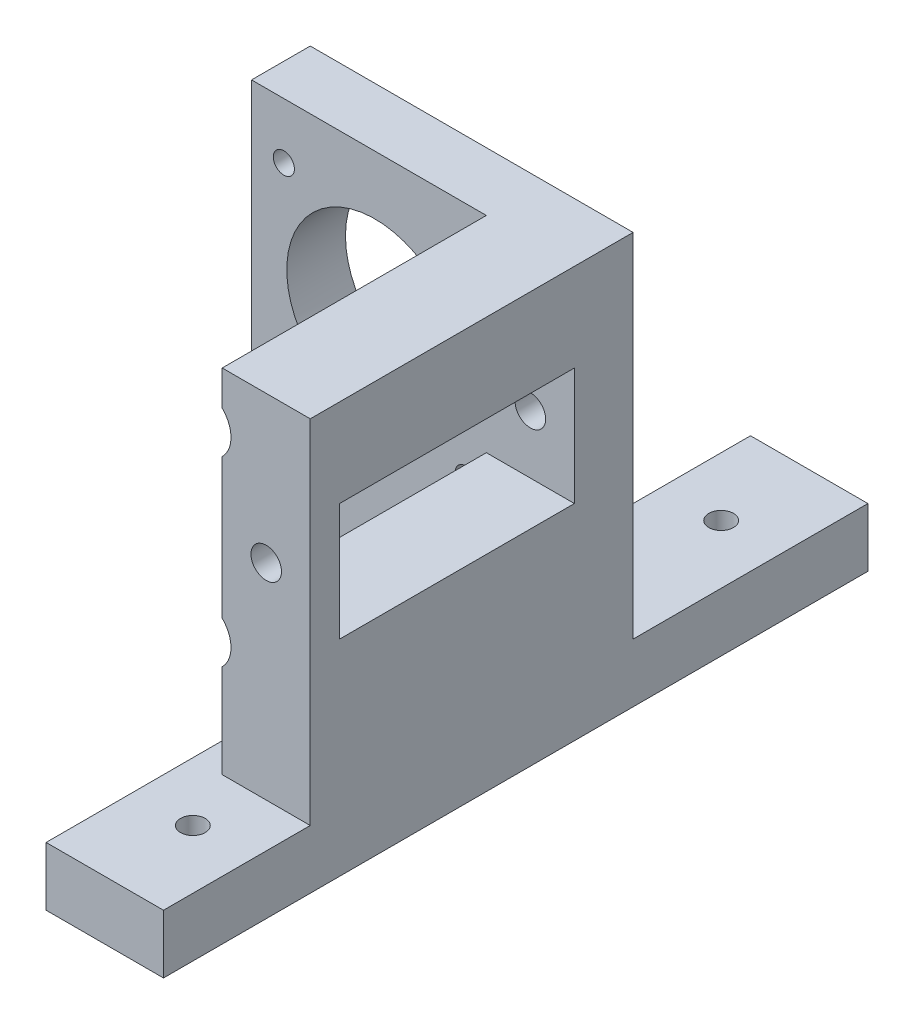
SolidWorks part; units mm, degrees
ref_plane "Front Plane" through (0, 0, 0) normal (0, 0, 1) x (1, 0, 0)
ref_plane "Top Plane" through (0, 0, 0) normal (0, 1, 0) x (1, 0, 0)
ref_plane "Right Plane" through (0, 0, 0) normal (1, 0, 0) x (0, 0, -1)
sketch "Sketch4" plane through (0, 0, 0) normal (0, 1, 0) x (1, 0, 0)
  line L1 (0, 0) -> (40, 0)
  line L2 (0, 0) -> (0, 80)
  line L3 (0, 80) -> (40, 80)
  line L4 (40, 0) -> (40, 80)
  dimension "D1" = 80
  dimension "D2" = 40
extrude "Boss-Extrude4" add sketch "Sketch4" along normal blind 5
sketch "Sketch5" plane through (0, 5, 0) normal (0, 1, 0) x (1, 0, 0)
  line L0 (40, 40) -> (30, 40)
  line L1 (30, 30) -> (30, 50) construction
  line L2 (40, 50) -> (30, 50)
  line L3 (30, 50) -> (30, 55)
  line L4 (0, 80) -> (0, 0)
  line L5 (0, 0) -> (40, 0)
  line L6 (40, 0) -> (40, 80)
  line L7 (40, 80) -> (0, 80)
  line L8 (0, 80) -> (0, 0)
  line L9 (0, 0) -> (40, 0)
  line L10 (40, 0) -> (40, 80)
  line L11 (40, 80) -> (0, 80)
  line L12 (30, 55) -> (40, 55)
  line L13 (40, 55) -> (40, 50)
  line L14 (40, 30) -> (30, 30)
  line L15 (30, 30) -> (30, 25)
  line L16 (30, 25) -> (40, 25)
  line L17 (40, 25) -> (40, 30)
  point P9 (30, 40)
  line M11 (40, 0) -> (40, 80)
  dimension "D2" = 10
  dimension "D3" = 10
  dimension "D4" = 5
  dimension "D5" = 5
  dimension "D1" = 0
extrude "Boss-Extrude6" add sketch "Sketch5" along normal blind 50 contours L12 L3 L2 M11 | L15 L16 L10 L14 region at (35, 5, -52.5) region at (35, 5, -27.5)
sketch "Sketch7" plane through (0, 0, -50) normal (0, 0, 1) x (1, 0, 0)
  line L1 (30, 5) -> (40, 5)
  line L2 (30, 5) -> (30, 30)
  line L3 (30, 30) -> (40, 30)
  line L4 (40, 5) -> (40, 30)
  line L5 (40, 55) -> (40, 5) construction
  line L7 (30, 55) -> (40, 55)
  line L8 (30, 55) -> (30, 50)
  line L9 (30, 50) -> (40, 50)
  line L10 (40, 55) -> (40, 50)
  dimension "D1" = 25
  dimension "D2" = 10
  dimension "D3" = 5
extrude "Boss-Extrude7" add sketch "Sketch7" along normal up to surface (20 mm away) contours L8 L7 L10 L9 | L2 L1 L4 L3 up to face at (35, 30, -30)
sketch "Sketch8" plane through (0, 0, -80) normal (0, 0, -1) x (-1, 0, 0)
  line L4 (-40, 0) -> (0, 0)
  line L5 (0, 0) -> (0, 5)
  line L6 (0, 5) -> (-40, 5)
  line L7 (-40, 5) -> (-40, 0)
  line L8 (-40, 0) -> (0, 0)
  line L9 (0, 0) -> (0, 5)
  line L10 (0, 5) -> (-40, 5)
  line L11 (-40, 5) -> (-40, 0)
  dimension "D1" = 0
extrude "Boss-Extrude8" add sketch "Sketch8" along normal blind 20 contours L8 L9 L10 L11
sketch "Sketch9" plane through (0, 0, 0) normal (-1, 0, 0) x (0, 0, 1)
  line L4 (-100, 0) -> (0, 0)
  line L5 (0, 0) -> (0, 5)
  line L6 (0, 5) -> (-100, 5)
  line L7 (-100, 5) -> (-100, 0)
  line L8 (-100, 0) -> (0, 0)
  line L9 (0, 0) -> (0, 5)
  line L10 (0, 5) -> (-100, 5)
  line L11 (-100, 5) -> (-100, 0)
  dimension "D1" = 0
extrude "Boss-Extrude9" add sketch "Sketch9" along normal blind 10
sketch "Sketch10" plane through (30, 0, 0) normal (-1, 0, 0) x (0, 0, 1)
  line L0 (-25, 5) -> (-55, 5) construction
  line L1 (-55, 55) -> (-50, 55)
  line L2 (-55, 55) -> (-55, 5)
  line L3 (-55, 5) -> (-50, 5)
  line L4 (-50, 55) -> (-50, 5)
  dimension "D1" = 5
extrude "Boss-Extrude10" add sketch "Sketch10" along normal blind 40 contours L2 L1 L4 L3
sketch "Sketch11" plane through (0, 55, 0) normal (0, 1, 0) x (1, 0, 0)
  line L6 (40, 55) -> (-10, 55)
  line L7 (-10, 55) -> (-10, 50)
  line L8 (-10, 50) -> (30, 50)
  line L9 (30, 50) -> (30, 25)
  line L10 (30, 25) -> (40, 25)
  line L11 (40, 25) -> (40, 55)
  line L12 (40, 55) -> (-10, 55)
  line L13 (-10, 55) -> (-10, 50)
  line L14 (-10, 50) -> (30, 50)
  line L15 (30, 50) -> (30, 25)
  line L16 (30, 25) -> (40, 25)
  line L17 (40, 25) -> (40, 55)
  dimension "D1" = 0
extrude "Boss-Extrude11" add sketch "Sketch11" along normal blind 10
sketch "Sketch12" plane through (0, 0, -50) normal (0, 0, 1) x (1, 0, 0)
  line L0 (30, 50) -> (30, 30)
  line L1 (30, 40) -> (26, 40)
  line L2 (0.3934, 50.6066) -> (-3.227, 54.227)
  line L3 (-10, 61) -> (32, 61)
  line L4 (-10, 61) -> (-10, 19)
  line L5 (-10, 19) -> (32, 19)
  line L6 (32, 61) -> (32, 19)
  line L7 (-10, 61) -> (32, 19) construction
  line L8 (30, 30) -> (40, 30)
  line L9 (40, 30) -> (40, 50)
  line L10 (40, 50) -> (30, 50)
  line L11 (30, 50) -> (30, 65)
  line L12 (30, 65) -> (-10, 65)
  line L13 (-10, 65) -> (-10, 5)
  line L14 (-10, 5) -> (30, 5)
  line L15 (30, 5) -> (30, 30)
  line L16 (30, 30) -> (40, 30)
  line L17 (40, 30) -> (40, 50)
  line L18 (40, 50) -> (30, 50)
  line L19 (30, 50) -> (30, 65)
  line L20 (30, 65) -> (-10, 65)
  line L21 (-10, 65) -> (-10, 5)
  line L22 (-10, 5) -> (30, 5)
  line L23 (30, 5) -> (30, 30)
  line L24 (-10, 19) -> (32, 61) construction
  line L25 (-2.6998, 24.5002) -> (-4.4998, 24.5002) construction
  line L26 (24.6998, 24.5002) -> (-2.6998, 24.5002)
  line L27 (26.4998, 26.3002) -> (26.4998, 53.6998)
  line L28 (24.6998, 55.4998) -> (-2.6998, 55.4998)
  line L29 (-4.4998, 26.3002) -> (-4.4998, 53.6998)
  line L30 (26.4998, 24.5002) -> (-4.4998, 55.4998) construction
  line L31 (26.4998, 55.4998) -> (-4.4998, 24.5002) construction
  line L32 (26.4998, 24.5002) -> (24.6998, 24.5002) construction
  line L33 (26.4998, 24.5002) -> (26.4998, 26.3002) construction
  line L34 (26.4998, 53.6998) -> (26.4998, 55.4998) construction
  line L35 (26.4998, 55.4998) -> (24.6998, 55.4998) construction
  line L36 (11, 40) -> (0.3934, 50.6066) construction
  line L37 (26, 40) -> (11, 40) construction
  line L38 (-3.227, 54.227) -> (-4.4998, 55.4998) construction
  line L39 (-4.4998, 53.6998) -> (-4.4998, 55.4998) construction
  line L40 (-2.6998, 55.4998) -> (-4.4998, 55.4998) construction
  line L41 (-4.4998, 24.5002) -> (-4.4998, 26.3002) construction
  circle A0 centre (11, 40) radius 15
  circle A1 centre (-4.4998, 55.4998) radius 1.8
  circle A2 centre (26.4998, 55.4998) radius 1.8
  circle A3 centre (26.4998, 24.5002) radius 1.8
  circle A4 centre (-4.4998, 24.5002) radius 1.8
  dimension "D2" = 19
  dimension "D3" = 30
  dimension "D6" = 3.6
  dimension "D7" = 3.6
  dimension "D1" = 0
  dimension "D4" = 42
  dimension "D5" = 21.92
extrude "Cut-Extrude1" cut sketch "Sketch12" against normal up to surface (5 mm away) contours A0 | A1 | A2 | A4 | A3 region at (11, 40, -50) region at (-4.4998, 55.4998, -50) up to face at (15, 35, -55)
sketch "Sketch13" plane through (0, 0, -50) normal (0, 0, 1) x (1, 0, 0)
  line L0 (40, 40) -> (35, 40) construction
  line L8 (30, 30) -> (40, 30)
  line L9 (40, 30) -> (40, 50)
  line L10 (40, 50) -> (30, 50)
  line L11 (30, 50) -> (30, 65)
  line L12 (30, 65) -> (-10, 65)
  line L13 (-10, 65) -> (-10, 5)
  line L14 (-10, 5) -> (30, 5)
  line L15 (30, 5) -> (30, 30)
  line L16 (30, 30) -> (40, 30)
  line L17 (40, 30) -> (40, 50)
  line L18 (40, 50) -> (30, 50)
  line L19 (30, 50) -> (30, 65)
  line L20 (30, 65) -> (-10, 65)
  line L21 (-10, 65) -> (-10, 5)
  line L22 (-10, 5) -> (30, 5)
  line L23 (30, 5) -> (30, 30)
  circle A0 centre (35, 40) radius 2.25
  dimension "D3" = 4.5
  dimension "D2" = 5
  dimension "D1" = 0
extrude "Cut-Extrude2" cut sketch "Sketch13" against normal through all both and the other way through all contours A0
sketch "Sketch14" plane through (0, 0, -25) normal (0, 0, 1) x (1, 0, 0)
  circle A0 centre (35, 40) radius 2.25 construction
  circle A1 centre (35, 40) radius 2.25
  circle A2 centre (35, 40) radius 4
  dimension "D1" = 8
extrude "Cut-Extrude4" cut sketch "Sketch14" against normal blind 2 contours A1 | A2
sketch "Sketch15" plane through (0, 0, -55) normal (0, 0, -1) x (-1, 0, 0)
  circle A0 centre (-35, 40) radius 2.25 construction
  circle A1 centre (-35, 40) radius 2.25
  circle A2 centre (-35, 40) radius 4
  dimension "D1" = 8
extrude "Cut-Extrude5" cut sketch "Sketch15" against normal blind 2
sketch "Sketch17" plane through (0, 0, -25) normal (0, 0, 1) x (1, 0, 0)
  line L0 (26.4998, 55.4998) -> (26.4998, 24.5002)
  circle A0 centre (26.4998, 55.4998) radius 1.8 construction
  circle A1 centre (26.4998, 55.4998) radius 1.8
  circle A2 centre (26.4998, 55.4998) radius 5
  circle A3 centre (26.4998, 24.5002) radius 5
  line M4 (30, 65) -> (30, 5)
  dimension "D1" = 10
  dimension "D2" = 10
extrude "Cut-Extrude6" cut sketch "Sketch17" against normal up to surface (25 mm away) contours A2 A1 M4 | A3 M4 | A3 M4 | A2 M4 region at (21.9924, 57.3406, -25) region at (26.0733, 24.5002, -25) region at (30.6084, 55.4998, -25) region at (30.6084, 24.5002, -25) up to face at (37.25, 40, -50)
sketch "Sketch19" plane through (0, 0, -55) normal (0, 0, -1) x (-1, 0, 0)
  line L4 (10, 5) -> (10, 65)
  line L5 (10, 65) -> (-40, 65)
  line L6 (-40, 65) -> (-40, 5)
  line L7 (-40, 5) -> (10, 5)
  line L8 (10, 5) -> (10, 65)
  line L9 (10, 65) -> (-40, 65)
  line L10 (-40, 65) -> (-40, 5)
  line L11 (-40, 5) -> (10, 5)
  circle A0 centre (4.4998, 55.4998) radius 1.8 construction
  circle A1 centre (4.4998, 24.5002) radius 1.8 construction
  circle A2 centre (-26.4998, 24.5002) radius 1.8 construction
  circle A3 centre (-11, 40) radius 15 construction
  circle A4 centre (-35, 40) radius 4 construction
  circle A6 centre (-26.4998, 55.4998) radius 1.8 construction
  circle A7 centre (4.4998, 55.4998) radius 1.8
  circle A8 centre (4.4998, 24.5002) radius 1.8
  circle A9 centre (-26.4998, 24.5002) radius 1.8
  circle A10 centre (-11, 40) radius 15
  circle A11 centre (-35, 40) radius 4
  circle A13 centre (-26.4998, 55.4998) radius 1.8
  dimension "D1" = 0
extrude "Boss-Extrude13" add sketch "Sketch19" along normal blind 5
sketch "Sketch20" plane through (0, 0, -53) normal (0, 0, -1) x (-1, 0, 0)
  circle A0 centre (-35, 40) radius 2.25 construction
  circle A1 centre (-35, 40) radius 4
  circle A2 centre (-35, 40) radius 4
  circle A3 centre (-35, 40) radius 2.25
  dimension "D1" = 0
extrude "Boss-Extrude14" add sketch "Sketch20" along normal blind 5
sketch "Sketch21" plane through (40, 0, 0) normal (1, 0, 0) x (0, 0, -1)
  line L0 (50, 50) -> (50, 30) construction
  line L1 (30, 50) -> (30, 30) construction
  line L2 (30, 50) -> (50, 50) construction
  line L3 (30, 30) -> (50, 30) construction
  line L4 (50, 50) -> (50, 30)
  line L5 (30, 50) -> (30, 30)
  line L6 (30, 50) -> (50, 50)
  line L7 (30, 30) -> (50, 30)
  line L8 (100, 5) -> (60, 5)
  line L9 (60, 5) -> (60, 65)
  line L10 (60, 65) -> (25, 65)
  line L11 (25, 65) -> (25, 5)
  line L12 (25, 5) -> (0, 5)
  line L13 (0, 5) -> (0, 0)
  line L14 (0, 0) -> (100, 0)
  line L15 (100, 0) -> (100, 5)
  line L16 (100, 5) -> (60, 5)
  line L17 (60, 5) -> (60, 65)
  line L18 (60, 65) -> (25, 65)
  line L19 (25, 65) -> (25, 5)
  line L20 (25, 5) -> (0, 5)
  line L21 (0, 5) -> (0, 0)
  line L22 (0, 0) -> (100, 0)
  line L23 (100, 0) -> (100, 5)
  dimension "D1" = 0
extrude "Boss-Extrude15" add sketch "Sketch21" along normal blind 5
sketch "Sketch22" plane through (0, 0, -60) normal (0, 0, -1) x (-1, 0, 0)
  circle A0 centre (-35, 40) radius 4 construction
  circle A1 centre (-35, 40) radius 4
extrude "Boss-Extrude16" add sketch "Sketch22" against normal up to surface (10 mm away) up to face at (26.0833, 38.3333, -50)
sketch "Sketch23" plane through (0, 0, -25) normal (0, 0, 1) x (1, 0, 0)
  circle A0 centre (35, 40) radius 4 construction
  circle A1 centre (35, 40) radius 4
extrude "Boss-Extrude17" add sketch "Sketch23" against normal up to surface (5 mm away) up to face at (37.25, 40, -30)
sketch "Sketch24" plane through (0, 0, -30) normal (0, 0, -1) x (-1, 0, 0)
  line L0 (-30, 30) -> (-45, 50) construction
  line L1 (-30, 50) -> (-45, 30) construction
  line L4 (-30, 50) -> (-45, 50)
  line L5 (-45, 50) -> (-45, 30)
  line L6 (-45, 30) -> (-30, 30)
  line L7 (-30, 30) -> (-30, 50)
  line L8 (-30, 50) -> (-45, 50)
  line L9 (-45, 50) -> (-45, 30)
  line L10 (-45, 30) -> (-30, 30)
  line L11 (-30, 30) -> (-30, 50)
  circle A0 centre (-37.5, 40) radius 2.6
  dimension "D2" = 5.2
  dimension "D1" = 0
extrude "Cut-Extrude7" cut sketch "Sketch24" against normal through all both and the other way through all contours A0
sketch "Sketch25" plane through (0, 0, 0) normal (0, -1, 0) x (1, 0, 0)
  line L4 (45, 0) -> (-10, 0)
  line L5 (-10, 0) -> (-10, -100)
  line L6 (-10, -100) -> (45, -100)
  line L7 (45, -100) -> (45, 0)
  line L8 (45, 0) -> (-10, 0)
  line L9 (-10, 0) -> (-10, -100)
  line L10 (-10, -100) -> (45, -100)
  line L11 (45, -100) -> (45, 0)
  dimension "D1" = 0
extrude "Boss-Extrude18" add sketch "Sketch25" along normal blind 5
sketch "Sketch26" plane through (0, 0, 0) normal (0, 0, 1) x (1, 0, 0)
  line L4 (-10, 5) -> (-10, -5)
  line L5 (-10, -5) -> (45, -5)
  line L6 (45, -5) -> (45, 5)
  line L7 (45, 5) -> (-10, 5)
  line L8 (-10, 5) -> (-10, -5)
  line L9 (-10, -5) -> (45, -5)
  line L10 (45, -5) -> (45, 5)
  line L11 (45, 5) -> (-10, 5)
  dimension "D1" = 0
extrude "Boss-Extrude19" add sketch "Sketch26" along normal blind 20
sketch "Sketch27" plane through (30, 0, 0) normal (-1, 0, 0) x (0, 0, 1)
  line L1 (-30, 50) -> (-25, 50)
  line L2 (-30, 50) -> (-30, 30)
  line L3 (-30, 30) -> (-25, 30)
  line L4 (-25, 50) -> (-25, 30)
  line L5 (-25, 51.9293) -> (-25, 28.0707) construction
  dimension "D1" = 5
  dimension "D2" = 20
extrude "Cut-Extrude8" cut sketch "Sketch27" against normal blind 15
sketch "Sketch28" plane through (0, 0, -25) normal (0, 0, 1) x (1, 0, 0)
  line L5 (45, 5) -> (45, 30)
  line L6 (45, 30) -> (30, 30)
  line L7 (30, 30) -> (30, 28.0707)
  line L8 (30, 20.9297) -> (30, 5)
  line L9 (30, 5) -> (45, 5)
  line L10 (45, 5) -> (45, 30)
  line L11 (45, 30) -> (30, 30)
  line L12 (30, 30) -> (30, 28.0707)
  line L13 (30, 20.9297) -> (30, 5)
  line L14 (30, 5) -> (45, 5)
  line L15 (30, 51.9293) -> (30, 50)
  line L16 (30, 50) -> (45, 50)
  line L17 (45, 50) -> (45, 65)
  line L18 (45, 65) -> (30, 65)
  line L19 (30, 65) -> (30, 59.0703)
  line L20 (30, 51.9293) -> (30, 50)
  line L21 (30, 50) -> (45, 50)
  line L22 (45, 50) -> (45, 65)
  line L23 (45, 65) -> (30, 65)
  line L24 (30, 65) -> (30, 59.0703)
  arc A1 (30, 20.9297) -> (30, 28.0707) centre (26.4998, 24.5002) ccw
  arc A2 (30, 20.9297) -> (30, 28.0707) centre (26.4998, 24.5002) ccw
  arc A3 (30, 51.9293) -> (30, 59.0703) centre (26.4998, 55.4998) ccw
  arc A4 (30, 51.9293) -> (30, 59.0703) centre (26.4998, 55.4998) ccw
  dimension "D1" = 0
  dimension "D2" = 0
extrude "Boss-Extrude20" add sketch "Sketch28" along normal blind 20
sketch "Sketch29" plane through (0, 30, 0) normal (0, 1, 0) x (1, 0, 0)
  line L7 (30, 5) -> (45, 5)
  line L8 (30, 5) -> (30, 10)
  line L9 (30, 10) -> (45, 10)
  line L10 (45, 5) -> (45, 10)
  line L11 (45, 5) -> (45, 50) construction
  dimension "D1" = 5
  dimension "D2" = 15
extrude "Boss-Extrude21" add sketch "Sketch29" along normal blind 20
sketch "Sketch30" plane through (0, 0, -60) normal (0, 0, -1) x (-1, 0, 0)
  circle A0 centre (-37.5, 40) radius 2.6 construction
  circle A1 centre (-37.5, 40) radius 2.6
extrude "Cut-Extrude9" cut sketch "Sketch30" against normal blind 60
sketch "Sketch31" plane through (0, 5, 0) normal (0, 1, 0) x (1, 0, 0)
  line L0 (25, -20) -> (25, 50)
  line L1 (25, -400) -> (25, 100) construction
  line L2 (25, 60) -> (25, 100)
  line L4 (-10, 100) -> (-10, 60)
  line L5 (-10, 60) -> (45, 60)
  line L6 (45, 60) -> (45, 100)
  line L7 (45, 100) -> (-10, 100)
  line L8 (-10, 100) -> (-10, 60)
  line L9 (-10, 60) -> (25, 60)
  line L11 (25, 100) -> (-10, 100)
  line L14 (45, 5) -> (30, 5)
  line L15 (30, 5) -> (30, 50)
  line L16 (30, 50) -> (-10, 50)
  line L17 (-10, 50) -> (-10, -20)
  line L18 (-10, -20) -> (45, -20)
  line L19 (45, -20) -> (45, 5)
  line L22 (25, 50) -> (-10, 50)
  line L23 (-10, 50) -> (-10, -20)
  line L24 (-10, -20) -> (25, -20)
  dimension "D3" = 35
  dimension "D1" = 0
  dimension "D2" = 0
extrude "Cut-Extrude10" cut sketch "Sketch31" against normal blind 10
sketch "Sketch32" plane through (0, 5, 0) normal (0, 1, 0) x (1, 0, 0)
  line L0 (35, -20) -> (35, -5) construction
  line L1 (45, -20) -> (25, -20) construction
  line L2 (35, 100) -> (35, 85) construction
  line L3 (25, 100) -> (45, 100) construction
  circle A0 centre (35, 85) radius 2.1
  circle A1 centre (35, -5) radius 2.1
  dimension "D3" = 4.2
  dimension "D4" = 4.2
  dimension "D1" = 15
  dimension "D2" = 15
extrude "Cut-Extrude11" cut sketch "Sketch32" against normal blind 10
